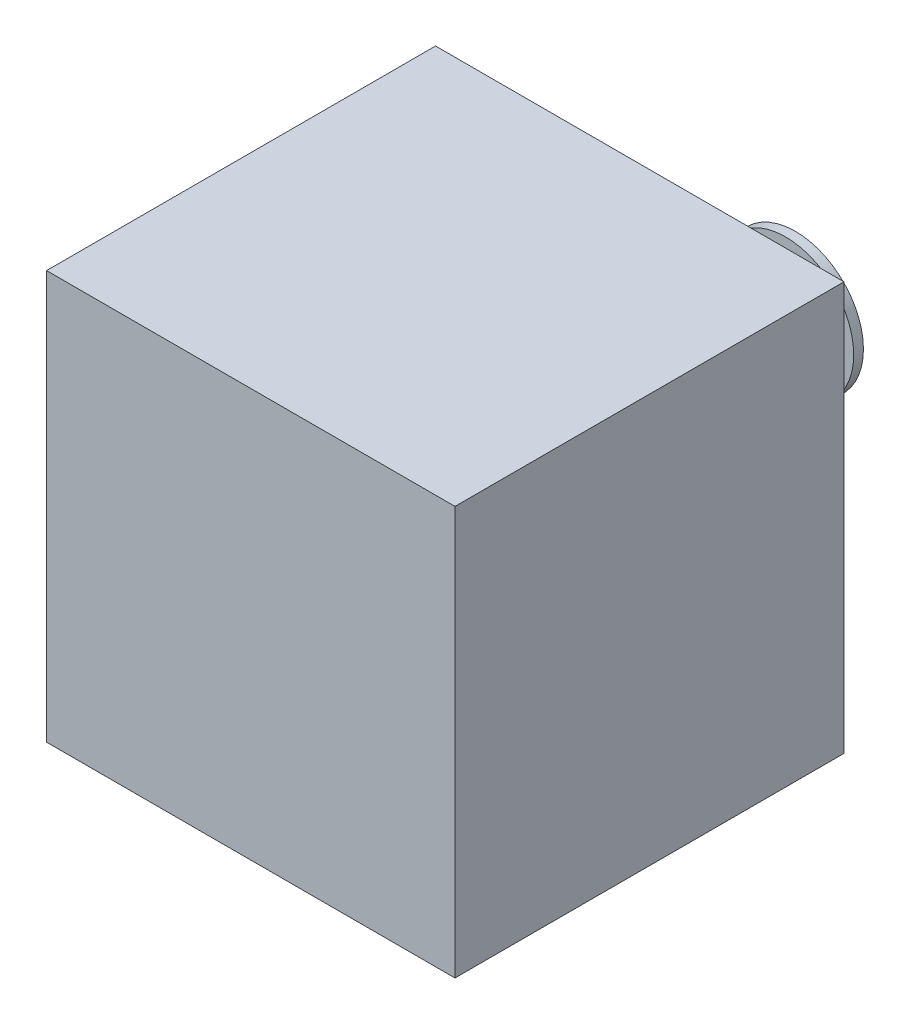
SolidWorks part; units mm, degrees
ref_plane "前视基准面" through (0, 0, 0) normal (0, 0, 1) x (1, 0, 0)
ref_plane "上视基准面" through (0, 0, 0) normal (0, 1, 0) x (1, 0, 0)
ref_plane "右视基准面" through (0, 0, 0) normal (1, 0, 0) x (0, 0, -1)
sketch "草图1" plane through (0, 0, 0) normal (0, 0, 1) x (1, 0, 0)
  line L1 (-21, -21) -> (21, -21)
  line L2 (-21, -21) -> (-21, 21)
  line L3 (-21, 21) -> (21, 21)
  line L4 (21, -21) -> (21, 21)
  line L5 (-21, -21) -> (21, 21) construction
  line L6 (-21, 21) -> (21, -21) construction
  circle A0 centre (0, 0) radius 11.5
  circle A1 centre (0, 0) radius 2.5
  point P0 (0, 0)
  dimension "D3" = 23
  dimension "D4" = 5
  dimension "D1" = 42
  dimension "D2" = 42
extrude "凸台-拉伸1" add sketch "草图1" along normal blind 40 contours L3 L4 L1 L2
extrude "凸台-拉伸2" add sketch "草图1<3>" against normal blind 2 contours A0
sketch "草图1<3>" plane through (0, 0, 0) normal (0, 0, 1) x (1, 0, 0) same geometry as "草图1"
extrude "凸台-拉伸3" add sketch "草图1<4>" against normal blind 16 contours A1
sketch "草图1<4>" plane through (0, 0, 0) normal (0, 0, 1) x (1, 0, 0) same geometry as "草图1"
sketch "草图2" plane through (0, 0, 0) normal (0, 1, 0) x (1, 0, 0)
  line L0 (2.5, 16) -> (7, 16)
  line L1 (7, 16) -> (7, 15)
  line L2 (7, 15) -> (6, 15)
  line L3 (6, 15) -> (6, 9)
  line L4 (6, 9) -> (7, 9)
  line L5 (7, 9) -> (7, 8)
  line L6 (7, 8) -> (2.5, 8)
  line L7 (2.5, 2) -> (2.5, 16) construction
  line L8 (0, -1000) -> (0, 49000) construction
  line L9 (2.5, 16) -> (2.5, 8)
  dimension "D1" = 1
  dimension "D2" = 1
  dimension "D3" = 6
  dimension "D4" = 6
  dimension "D5" = 7
revolve "旋转1" add sketch "草图2" angle 360 about L8
